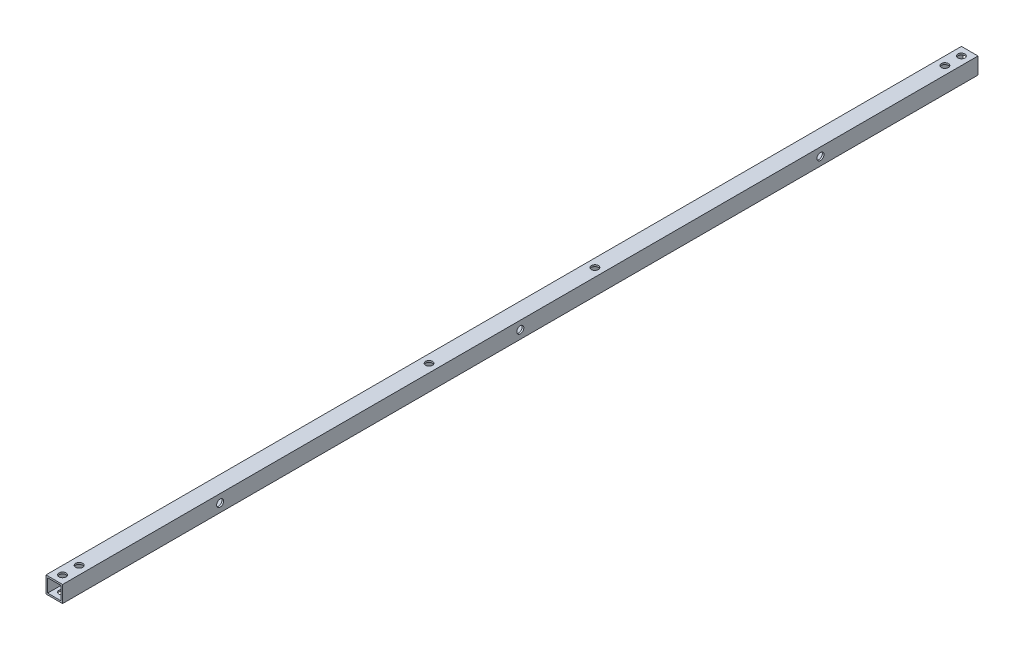
SolidWorks part; units mm, degrees
ref_plane "Front Plane" through (0, 0, 0) normal (0, 0, 1) x (1, 0, 0)
ref_plane "Top Plane" through (0, 0, 0) normal (0, 1, 0) x (1, 0, 0)
ref_plane "Right Plane" through (0, 0, 0) normal (1, 0, 0) x (0, 0, -1)
sketch "Sketch1" plane through (0, 0, 0) normal (0, 0, 1) x (1, 0, 0)
  line L1 (0, 0) -> (10, 0)
  line L2 (0, 0) -> (0, 10)
  line L3 (0, 10) -> (10, 10)
  line L4 (10, 0) -> (10, 10)
  line L5 (1, 9) -> (9, 9)
  line L6 (1, 9) -> (1, 1)
  line L7 (1, 1) -> (9, 1)
  line L8 (9, 9) -> (9, 1)
  dimension "D1" = 10
  dimension "D2" = 10
  dimension "D3" = 8
  dimension "D4" = 8
  dimension "D5" = 1
  dimension "D6" = 1
extrude "Boss-Extrude1" add sketch "Sketch1" along normal blind 552
sketch "Sketch2" plane through (0, 10, 0) normal (0, 1, 0) x (1, 0, 0)
  line L0 (10, 0) -> (0, 0) construction
  line L1 (10, -552) -> (10, 0) construction
  line L2 (0, -552) -> (0, 0) construction
  line L4 (10, -552) -> (0, -552) construction
  circle A0 centre (5, -5) radius 2.125
  circle A1 centre (5, -15) radius 2.125
  circle A2 centre (5, -537) radius 2.125
  circle A3 centre (5, -547) radius 2.125
  dimension "D1" = 4.25
  dimension "D2" = 4.25
  dimension "D7" = 4.25
  dimension "D8" = 4.25
  dimension "D9" = 5
  dimension "D10" = 5
  dimension "D11" = 15
  dimension "D12" = 5
  dimension "D3" = 5
  dimension "D4" = 15
  dimension "D5" = 5
  dimension "D6" = 5
extrude "Cut-Extrude1" cut sketch "Sketch2" against normal blind 116
sketch "Sketch3" plane through (0, 0, 0) normal (0, -1, 0) x (1, 0, 0)
  line L0 (10, 552) -> (10, 0) construction
  line L1 (0, 0) -> (10, 0) construction
  line L2 (0, 552) -> (10, 552) construction
  circle A0 centre (5, 326) radius 2.1
  circle A1 centre (5, 226) radius 2.125
  dimension "D1" = 4.25
  dimension "D2" = 5
  dimension "D3" = 226
  dimension "4.25" = 4.2
  dimension "D5" = 5
  dimension "D6" = 226
extrude "Cut-Extrude2" cut sketch "Sketch3" against normal blind 10
sketch "Sketch5" plane through (10, 0, 0) normal (1, 0, 0) x (0, 0, -1)
  line L0 (0, 0) -> (0, 10) construction
  line L1 (-552, 0) -> (-552, 10) construction
  line L2 (-552, 0) -> (0, 0) construction
  circle A0 centre (-457, 5) radius 2.125
  circle A1 centre (-95, 5) radius 2.125
  circle A2 centre (-276, 5) radius 2.125
  dimension "D1" = 4.25
  dimension "D2" = 4.25
  dimension "D3" = 4.25
  dimension "D4" = 95
  dimension "D5" = 95
  dimension "D6" = 276
  dimension "D7" = 5
extrude "Cut-Extrude3" cut sketch "Sketch5" against normal blind 10
